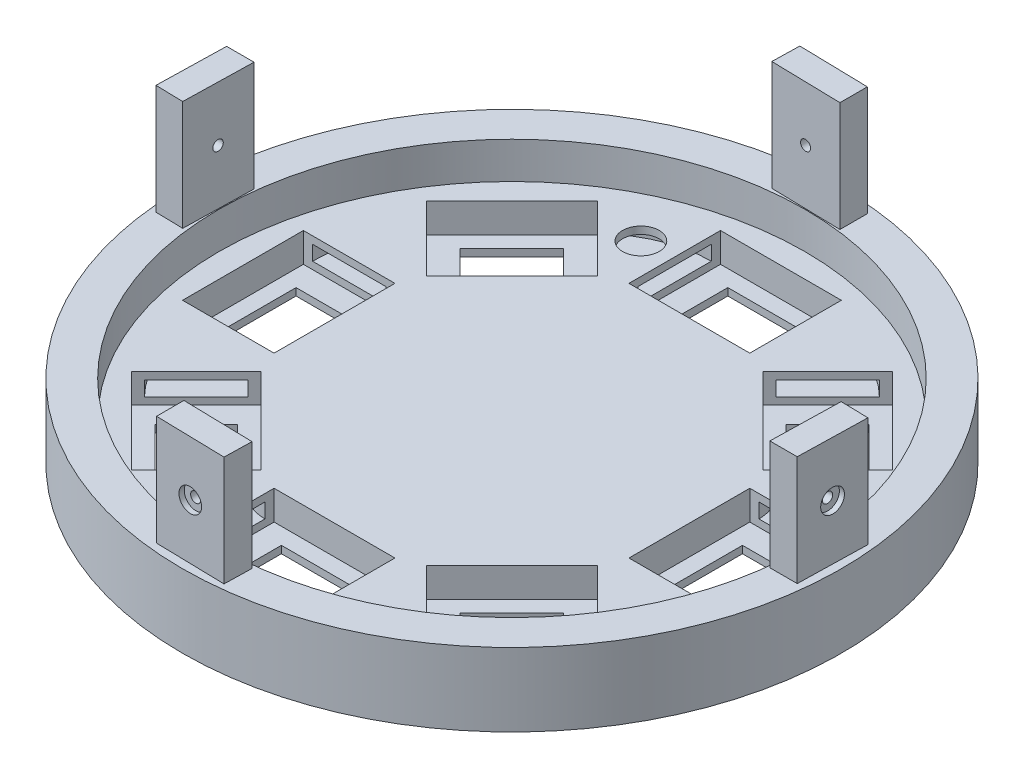
SolidWorks part; units mm, degrees
ref_plane "Front Plane" through (0, 0, 0) normal (0, 0, 1) x (1, 0, 0)
ref_plane "Top Plane" through (0, 0, 0) normal (0, 1, 0) x (1, 0, 0)
ref_plane "Right Plane" through (0, 0, 0) normal (1, 0, 0) x (0, 0, -1)
sketch "Sketch2" plane through (0, 0, 0) normal (0, 1, 0) x (1, 0, 0)
  circle A0 centre (0, 0) radius 45
  dimension "D1" = 90
extrude "Boss-Extrude1" add sketch "Sketch2" along normal blind 10
sketch "Sketch3" plane through (0, 10, 0) normal (0, 1, 0) x (1, 0, 0)
  circle A3 centre (0, 0) radius 40
  circle A4 centre (0, 0) radius 40
  dimension "D1" = 5
extrude "Cut-Extrude1" cut sketch "Sketch3" against normal blind 5
sketch "Sketch4" plane through (0, 5, 0) normal (0, 1, 0) x (1, 0, 0)
  line L0 (0, 0) -> (0, 40) construction
  line L5 (-8.25, 36.7275) -> (8.25, 36.7275)
  line L6 (-8.25, 36.7275) -> (-8.25, 24.2275)
  line L7 (-8.25, 24.2275) -> (8.25, 24.2275)
  line L8 (8.25, 36.7275) -> (8.25, 24.2275)
  line L9 (20.1366, 31.8039) -> (11.2978, 22.965)
  line L10 (20.1366, 31.8039) -> (31.8039, 20.1366)
  line L11 (31.8039, 20.1366) -> (22.965, 11.2978)
  line L12 (11.2978, 22.965) -> (22.965, 11.2978)
  line L13 (36.7275, 8.25) -> (24.2275, 8.25)
  line L14 (36.7275, 8.25) -> (36.7275, -8.25)
  line L15 (36.7275, -8.25) -> (24.2275, -8.25)
  line L16 (24.2275, 8.25) -> (24.2275, -8.25)
  line L17 (31.8039, -20.1366) -> (22.965, -11.2978)
  line L18 (31.8039, -20.1366) -> (20.1366, -31.8039)
  line L19 (20.1366, -31.8039) -> (11.2978, -22.965)
  line L20 (22.965, -11.2978) -> (11.2978, -22.965)
  line L21 (8.25, -36.7275) -> (8.25, -24.2275)
  line L22 (8.25, -36.7275) -> (-8.25, -36.7275)
  line L23 (-8.25, -36.7275) -> (-8.25, -24.2275)
  line L24 (8.25, -24.2275) -> (-8.25, -24.2275)
  line L25 (-20.1366, -31.8039) -> (-11.2978, -22.965)
  line L26 (-20.1366, -31.8039) -> (-31.8039, -20.1366)
  line L27 (-31.8039, -20.1366) -> (-22.965, -11.2978)
  line L28 (-11.2978, -22.965) -> (-22.965, -11.2978)
  line L29 (-36.7275, -8.25) -> (-24.2275, -8.25)
  line L30 (-36.7275, -8.25) -> (-36.7275, 8.25)
  line L31 (-36.7275, 8.25) -> (-24.2275, 8.25)
  line L32 (-24.2275, -8.25) -> (-24.2275, 8.25)
  line L33 (-31.8039, 20.1366) -> (-22.965, 11.2978)
  line L34 (-31.8039, 20.1366) -> (-20.1366, 31.8039)
  line L35 (-20.1366, 31.8039) -> (-11.2978, 22.965)
  line L36 (-22.965, 11.2978) -> (-11.2978, 22.965)
  circle A0 centre (0, 0) radius 40 construction
  point P10 (0, 36.7275)
  point P42 (0, 0)
  dimension "D2" = 16.5
  dimension "D3" = 12.5
  dimension "D1" = 8
extrude "Cut-Extrude2" cut sketch "Sketch4" against normal blind 4
sketch "Sketch6" plane through (0, 1, 0) normal (0, 1, 0) x (1, 0, 0)
  line L0 (0, 0) -> (0, 40) construction
  line L1 (-5, 26.4775) -> (5, 26.4775)
  line L2 (-5, 26.4775) -> (-5, 34.4775)
  line L3 (-5, 34.4775) -> (5, 34.4775)
  line L4 (5, 26.4775) -> (5, 34.4775)
  line L5 (-5, 26.4775) -> (5, 34.4775) construction
  line L6 (-5, 34.4775) -> (5, 26.4775) construction
  line L7 (-8.25, 30.4775) -> (8.25, 30.4775) construction
  line L8 (-8.25, 36.7275) -> (-8.25, 24.2275) construction
  circle A0 centre (0, 0) radius 40 construction
  point P0 (0, 30.4775)
  dimension "D1" = 10
  dimension "D2" = 8
extrude "Cut-Extrude3" cut sketch "Sketch6" against normal through all
pattern_circular "CirPattern1" count 8 over 360 about axis through (0, 5, 0) along (0, 1, 0) of "Cut-Extrude3"
sketch "Sketch7" plane through (-8.25, 0, 0) normal (1, 0, 0) x (0, 0, -1)
  line L0 (30.4775, 1) -> (30.4775, 5) construction
  line L1 (25.4775, 1.9966) -> (35.4775, 1.9966)
  line L2 (25.4775, 1.9966) -> (25.4775, 4.0034)
  line L3 (25.4775, 4.0034) -> (35.4775, 4.0034)
  line L4 (35.4775, 1.9966) -> (35.4775, 4.0034)
  line L5 (25.4775, 1.9966) -> (35.4775, 4.0034) construction
  line L6 (25.4775, 4.0034) -> (35.4775, 1.9966) construction
  line L7 (36.7275, 1) -> (24.2275, 1) construction
  line L8 (36.7275, 5) -> (24.2275, 5) construction
  point P0 (30.4775, 3)
  dimension "D1" = 10
ref_axis "Axis3" through (-8.25, 5, -19.9173) along (0, -1, 0)
revolve "Cut-Revolve1" cut sketch "Sketch7" angle 45 about axis through (-8.25, 5, -19.9173) along (0, -1, 0) reverse direction yes
ref_axis "Axis4" through (0, -0.5, 0) along (0, 1, 0)
pattern_circular "CirPattern8" count 8 over 360 about axis through (0, -0.5, 0) along (0, 1, 0) of "Cut-Revolve1"
sketch "Sketch10" plane through (0, 5, 0) normal (0, 1, 0) x (1, 0, 0)
  line L0 (-11.2978, 22.965) -> (-20.1366, 31.8039) construction
  line L1 (-8.25, 36.7275) -> (-8.25, 24.2275) construction
  circle A0 centre (-12.45, 30.057) radius 2.5
  point P2 (0, 0)
  dimension "D1" = 5
  dimension "D2" = 4.2
  dimension "D3" = 4.2
extrude "Cut-Extrude4" cut sketch "Sketch10" against normal up to next
sketch "Sketch11" plane through (0, 10, 0) normal (0, 1, 0) x (1, 0, 0)
  line L0 (40.2207, 4.7331) -> (40, -4.7858)
  line L1 (40, -4.7858) -> (43.7408, -4.7858)
  line L2 (43.7408, -4.7858) -> (43.9594, 4.6464)
  line L3 (43.9594, 4.6464) -> (40.2207, 4.7331)
  line L4 (0, 0) -> (45, 0) construction
  line L5 (41.8704, -4.7858) -> (42.09, 4.6897) construction
  circle A3 centre (0, 0) radius 45 construction
extrude "Boss-Extrude2" add sketch "Sketch11" along normal blind 15
pattern_circular "CirPattern9" count 4 over 360 about axis through (0, -0.5, 0) along (0, 1, 0) of "Boss-Extrude2"
sketch "Sketch13" plane through (1.016, 0, -43.8282) normal (0.0232, 0, -0.9997) x (-0.9997, 0, -0.0232)
  line L0 (0, 0) -> (0, 21.0762) construction
sketch "Sketch14" plane through (43.8282, 0, 1.016) normal (0.9997, 0, 0.0232) x (0.0232, 0, -0.9997)
  line L0 (0.9466, 10) -> (0.9466, 25) construction
  line L1 (-3.7708, 10) -> (5.6639, 10) construction
  line L2 (-3.7708, 25) -> (5.6639, 25) construction
  point P6 (0.9466, 17.5)
hole_wizard "CBORE for #00 Binding Head Machine Screw3" positions "3DSketch4" profile "Sketch15" counterbore size "#00" standard "ANSI Inch" end condition up to next
sketch3d "3DSketch4"
  point P0 (43.8501, 17.5, 0.0697)
sketch "Sketch15" plane through (43.8501, 17.5, 0.0697) normal (0, 1, 0) x (0.0232, 0, -0.9997)
  line L0 (0, 0) -> (0, 87.6799)
  line L1 (0, 87.6799) -> (0.6985, 87.6799)
  line L3 (0.6985, 87.6799) -> (0.6985, 0.7112)
  line L4 (0.6985, 0.7112) -> (1.5875, 0.7112)
  line L5 (1.5875, 0.7112) -> (1.5875, 0)
  line L7 (1.5875, 0) -> (0, 0)
  line L11 (0, -6.35) -> (0, 107.95) construction
  dimension "Thru Hole Dia." = 1.397
  dimension "Thru Hole Depth" = 87.6799
  dimension "C'Bore Dia." = 3.175
  dimension "C'Bore Depth" = 0.7112
pattern_circular "CirPattern10" count 4 over 360 about axis through (0, -0.5, 0) along (0, 1, 0) of "CBORE for #00 Binding Head Machine Screw3"
